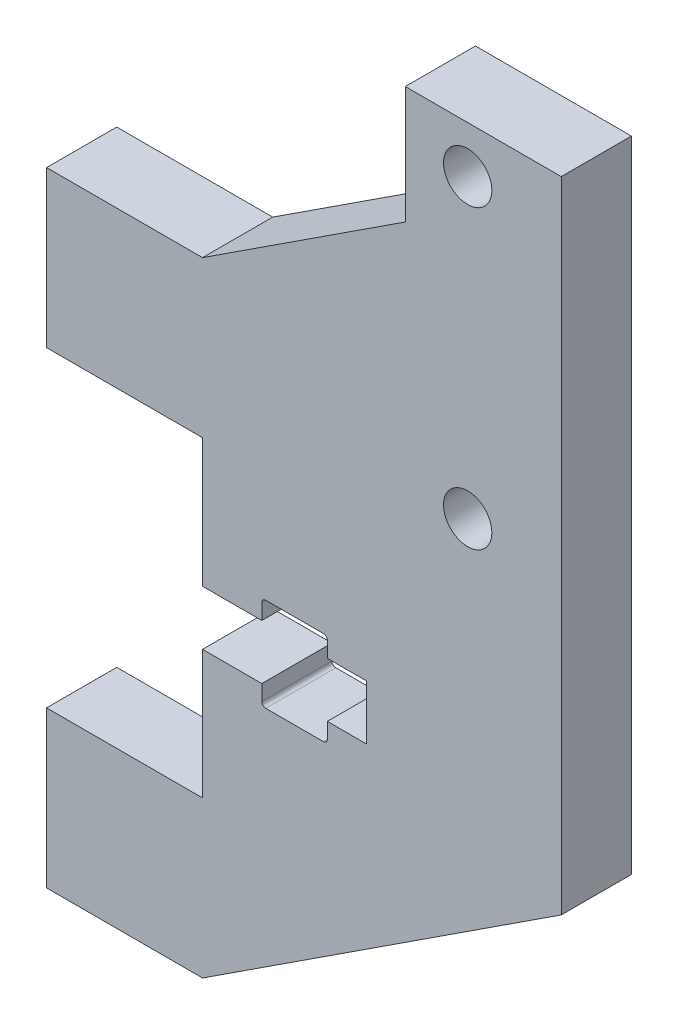
SolidWorks part; units mm, degrees
ref_plane "Front Plane" through (0, 0, 0) normal (0, 0, 1) x (1, 0, 0)
ref_plane "Top Plane" through (0, 0, 0) normal (0, 1, 0) x (1, 0, 0)
ref_plane "Right Plane" through (0, 0, 0) normal (1, 0, 0) x (0, 0, -1)
sketch "Sketch1" plane through (0, 0, 0) normal (0, 0, 1) x (1, 0, 0)
  line L0 (13, 3.4783) -> (0, -5)
  line L1 (0, -5) -> (-10, -5)
  line L2 (-10, -5) -> (-10, -15)
  line L3 (-10, -15) -> (0, -15)
  line L4 (0, -15) -> (0, -35)
  line L5 (0, -35) -> (-10, -35)
  line L6 (-10, -35) -> (-10, -45)
  line L7 (-10, -45) -> (0, -45)
  line L10 (0, -45) -> (23, -30)
  line L11 (23, -30) -> (23, 11)
  line L12 (23, 11) -> (13, 11)
  line L13 (13, 11) -> (13, 3.4783)
  line L15 (0, -5) -> (0, -45) construction
  line L16 (-10, -10) -> (0, -10) construction
  line L17 (-10, -40) -> (0, -40) construction
  line L18 (-10, -15) -> (-10, -35) construction
  line L19 (-10, -25) -> (0, -25) construction
  dimension "D2" = 10
  dimension "D3" = 10
  dimension "D4" = 10
  dimension "D5" = 15
  dimension "D8" = 10
  dimension "D10" = 13
  dimension "D6" = 15
  dimension "D7" = 16
extrude "Boss-Extrude1" add sketch "Sketch1" along normal blind 4.5
sketch "Sketch2" plane through (0, 0, 4.5) normal (0, 0, 1) x (1, 0, 0)
  line L0 (0, -25) -> (23, -25) construction
  line L1 (0, -15) -> (0, -35) construction
  line L3 (10.5, -26.75) -> (10.5, -23.25) construction
  line L4 (10.5, -23.25) -> (0, -23.25) construction
  line L5 (0, -26.75) -> (0, -23.25)
  line L6 (0, -23.25) -> (3.8, -23.25)
  line L7 (3.8, -23.25) -> (3.8, -22.25)
  line L8 (4.05, -22) -> (7.75, -22)
  line L9 (8, -22.25) -> (8, -23.25)
  line L10 (8, -23.25) -> (10.5, -23.25)
  line L11 (10.5, -23.25) -> (10.5, -26.75)
  line L12 (10.5, -26.75) -> (0, -26.75) construction
  line L13 (8, -26.75) -> (10.5, -26.75)
  line L14 (8, -27.75) -> (8, -26.75)
  line L15 (4.05, -28) -> (7.75, -28)
  line L16 (3.8, -26.75) -> (3.8, -27.75)
  line L17 (0, -26.75) -> (3.8, -26.75)
  line L18 (23, -30) -> (23, 11) construction
  arc A0 (7.75, -22) -> (8, -22.25) centre (7.75, -22.25) cw
  arc A1 (3.8, -22.25) -> (4.05, -22) centre (4.05, -22.25) cw
  arc A2 (3.8, -27.75) -> (4.05, -28) centre (4.05, -27.75) ccw
  arc A3 (7.75, -28) -> (8, -27.75) centre (7.75, -27.75) ccw
  point P15 (8, -22)
  point P18 (3.8, -22)
  point P27 (10.5, -25)
  point P29 (3.8, -28)
  point P30 (8, -28)
  dimension "D6" = 0.25
  dimension "D1" = 10.5
  dimension "D2" = 1.75
  dimension "D3" = 8
  dimension "D4" = 4.2
  dimension "D5" = 3
extrude "screw-cutout" cut sketch "Sketch2" against normal through all
sketch "Sketch3" plane through (0, 0, 4.5) normal (0, 0, 1) x (1, 0, 0)
  line L0 (17, 55) -> (17, -45) construction
  line L3 (13, 11) -> (13, 3.4783) construction
  line L5 (-10, -45) -> (0, -45) construction
  line L10 (10.5, -26.75) -> (10.5, -23.25) construction
  circle A1 centre (17, 8) radius 1.55
  circle A5 centre (17, -11) radius 1.55
  point P8 (10.5, -25)
  dimension "D4" = 3.1
  dimension "D11" = 3.1
  dimension "D6" = 4
  dimension "D12" = 19
  dimension "D2" = 14
extrude "Cut-Extrude2" cut sketch "Sketch3" against normal through all
sketch "Sketch4" plane through (0, 0, 4.5) normal (0, 0, 1) x (1, 0, 0)
  line L0 (17, -11) -> (17, 8) construction
  line L1 (17, -1.5) -> (13, -1.5) construction
  line L2 (13, 11) -> (13, 3.4783) construction
  line L4 (15, 2.5) -> (13, 2.5)
  line L5 (15, 2.5) -> (15, -5.5)
  line L6 (15, -5.5) -> (13, -5.5)
  line L7 (13, 2.5) -> (13, -5.5)
  line L8 (15, 2.5) -> (13, -5.5) construction
  line L9 (15, -5.5) -> (13, 2.5) construction
  circle A1 centre (17, 8) radius 1.55 construction
  circle A3 centre (17, -11) radius 1.55 construction
  point P11 (14, -1.5)
  dimension "D1" = 8
  dimension "D2" = 2
  dimension "D3" = 3
equation "\"X-ROD-SPACING\"=45"
equation "\"Y-ROD-SPACING\"=75"
equation "\"Z-ROD-SPACING\"=17.5"
equation "\"Y-BED-OFFSET\"=2"
equation "\"Y-BED-ROD-INSET\"=3.5"
equation "\"T-SLOT-NUT-FILLET-RADIUS\"=0.25"
equation "\"T-SLOT-SCREW-SHAFT-RADIUS\"=1.75"
equation "\"T-SLOT-SCREW-SHAFT-CUTOUT-LENGTH\"=10.5"
equation "\"T-SLOT-NUT-DEPTH\"=4.2"
equation "\"T-SLOT-NUT-WIDTH\"=3"
equation "\"T-SLOT-NUT-END-DISTANCE\"=8"
equation "\"ACRYLIC-THICKNESS\"=10"
equation "\"ACRYLIC-THICKNESS2\"=4.5"
equation "\"ACRYLIC-TAB-CUTOUT-SIZE\"=\"ACRYLIC-THICKNESS\"+\"ACRYLIC-TAB-TOLERANCE\"*2"
equation "\"ACRYLIC-TAB-WIDTH\"=\"ACRYLIC-THICKNESS\""
equation "\"ACRYLIC-M3-HOLE\"=3.1"
equation "\"SMOOTHROD-CAP-SCREW-DISTANCE\"=20"
equation "\"FRAME-WIDTH-INNER\"=370"
equation "\"NEMA17-HOLE-SPACING\"=31"
equation "\"NEMA17-CENTRAL-CUTOUT\"=22.5"
equation "\"Z-BRACKET-REACH\"=55"
equation "\"Z-ROD-INSET\"=16"
equation "\"TOP-BRACKET-SPACING\"=40"
equation "\"SMOOTHROD-X-LENGTH\"=350"
equation "\"SMOOTHROD-Y-LENGTH\"=350"
equation "\"SMOOTHROD-Z-LENGTH\"=350"
equation "\"SMOOTHROD-TIGHTENING-HEADROOM\"=.25"
equation "\"LEADSCREW-Z-LENGTH\"=300"
equation "\"SCREW-LENGTH-FRAME\"=\"ACRYLIC-THICKNESS\" + 10"
equation "\"SCREW-HEAD-RADIUS\"=6"
equation "\"PRINTED-X-SMOOTHROD-DIAMETER\"=8.2"
equation "\"PRINTED-X-SMOOTHROD-CUTOUT\"=10"
equation "\"PRINTED-X-BASE-HEIGHT\"=10"
equation "\"PRINTED-LM8UU-CUTOUT-SIZE\"=15.25"
equation "\"PRINTED-LM8UU-CUTOUT-LENGTH\"=24.5"
equation "\"PRINTED-X-IDLER-HEIGHT\"=16"
equation "\"PSU-MOUNTING-WIDTH\"=95"
equation "\"PSU-MOUNTING-HEIGHT\"=177"
equation "\"Y-BELT-TO-ROD-DISTANCE\"=20"
equation "\"SPOOL-HOLDER-ROD-SPACING\"=150"
equation "\"D1@Sketch1\"=\"ACRYLIC-TAB-WIDTH\""
equation "\"D2@Sketch1\"=\"ACRYLIC-TAB-WIDTH\""
equation "\"D3@Sketch1\"=\"ACRYLIC-THICKNESS\""
equation "\"D4@Sketch1\"=\"ACRYLIC-THICKNESS\""
equation "\"D1@Boss-Extrude1\"=\"ACRYLIC-THICKNESS2\""
equation "\"D1@Sketch2\"=\"T-SLOT-SCREW-SHAFT-CUTOUT-LENGTH\""
equation "\"D2@Sketch2\"=\"T-SLOT-SCREW-SHAFT-RADIUS\""
equation "\"D3@Sketch2\"=\"T-SLOT-NUT-END-DISTANCE\""
equation "\"D4@Sketch2\"=\"T-SLOT-NUT-DEPTH\""
equation "\"D5@Sketch2\"=\"T-SLOT-NUT-WIDTH\""
equation "\"D6@Sketch2\"=\"T-SLOT-NUT-FILLET-RADIUS\""
equation "\"D4@Sketch3\"=\"ACRYLIC-M3-HOLE\""
equation "\"D11@Sketch3\"=\"ACRYLIC-M3-HOLE\""
equation "\"Y-BED-SCREW-SPACING\"=209"
equation "\"Y-BED-SCREW-CUTOUT-SLOT-HEIGHT\"=2"
equation "\"ACRYLIC-TAB-TOLERANCE\"=.1"
equation "\"SCREW-LENGTH-MOTOR\"=\"ACRYLIC-THICKNESS\" + 5"
equation "\"SCREW-LENGTH-EXTRUDER\"=28"
equation "\"PRINTED-M3-HOLE\"=3.5"
equation "\"ACRYLIC-X-CARRIAGE-WIDTH\"=55"
equation "\"ACRYLIC-X-CARRIAGE-HEIGHT\"=75"
equation "\"ACRYLIC-X-CARRIAGE-LM8UU-CUTOUT-WIDTH\"=24.25"
equation "\"ACRYLIC-X-CARRIAGE-LM8UU-CUTOUT-HEIGHT\"=11.5"
equation "\"ACRYLIC-X-CARRIAGE-SCREW-SPACING-X\"=15"
equation "\"ACRYLIC-X-CARRIAGE-SCREW-SPACING-Y\"=33"
equation "\"ACRYLIC-X-CARRIAGE-CENTER-TAB-SPACING\"=14"
equation "\"ACRYLIC-X-CARRIAGE-EXTRUDER-OFFSET\"=26"
equation "\"ACRYLIC-X-CARRIAGE-EXTRUDER-ANGLE\"=90"
equation "\"ACRYLIC-X-CARRIAGE-EXTRUDER-SHELF-DEPTH\"=\"ACRYLIC-X-CARRIAGE-EXTRUDER-OFFSET\" + 28"
equation "\"ACRYLIC-X-CARRIAGE-EXTRUDER-BRACE-SPACING\"=23"
equation "\"ACRYLIC-X-CARRIAGE-EXTRUDER-BRACE-TAB-OFFSET\"=20"
equation "\"ACRYLIC-X-CARRIAGE-EXTRUDER-BRACE-HEIGHT\"=35"
equation "\"ACRYLIC-X-CARRIAGE-EXTRUDER-BRACE-SCREW-SPACING\"=22"
equation "\"ACRYLIC-X-CARRIAGE-DUAL-WIDTH-MULTIPLIER\"=1.65"
equation "\"ACRYLIC-X-CARRIAGE-DUAL-HOTEND-SPACING\"=42"
equation "\"ACRYLIC-X-CARRIAGE-DUAL-WIDTH\"=75"
equation "\"ACRYLIC-X-CARRIAGE-DUAL-HOTEND-SEPARATION\"=36"
equation "\"ACRYLIC-X-CARRIAGE-DUAL-MOUNT-PLATE-DEPTH\"=75"
equation "\"ACRYLIC-X-CARRIAGE-DUAL-MOUNT-BRACE-WIDTH\"=33"
equation "\"ACRYLIC-X-CARRIAGE-DUAL-MOUNT-SCREW-WIDTH\"=40"
equation "\"BLOWER-FAN-WIDTH\"=15"
